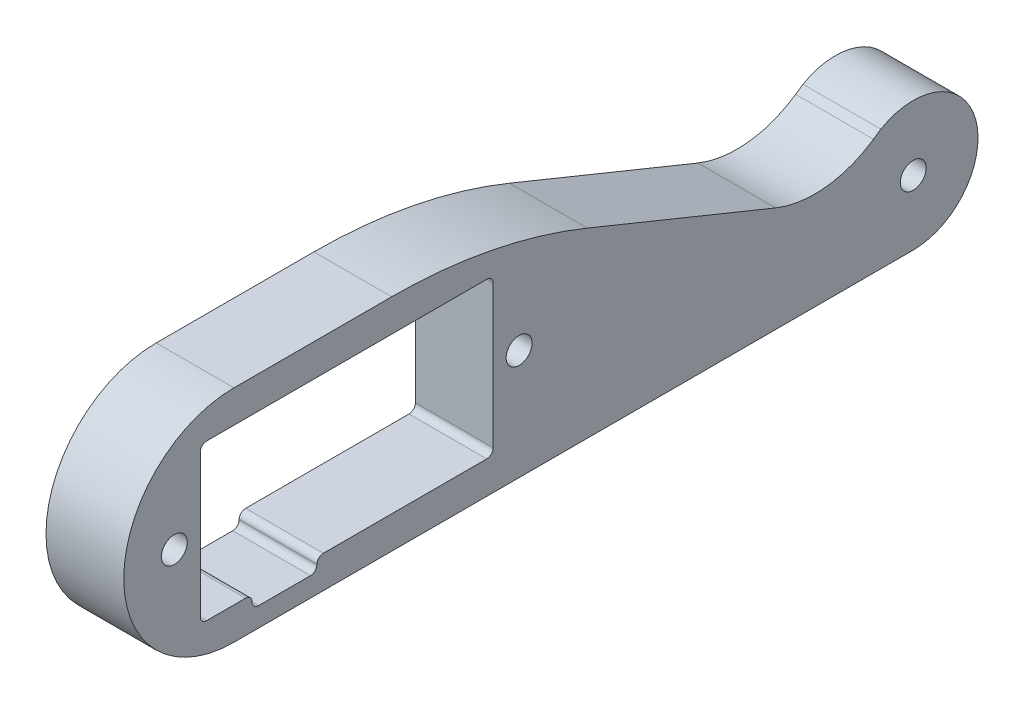
SolidWorks part; units mm, degrees
ref_plane "Piano frontale" through (0, 0, 0) normal (0, 0, 1) x (1, 0, 0)
ref_plane "Piano superiore" through (0, 0, 0) normal (0, 1, 0) x (1, 0, 0)
ref_plane "Piano destro" through (0, 0, 0) normal (1, 0, 0) x (0, 0, -1)
sketch "Schizzo1" plane through (0, 0, 0) normal (1, 0, 0) x (0, 0, -1)
  line L0 (2.6, 14.5) -> (22.6, 14.5)
  line L1 (0, 12) -> (22.6, 12)
  line L2 (0, 12) -> (0, 0)
  line L3 (0, 0) -> (22.6, 0)
  line L4 (22.6, 12) -> (22.6, 0)
  line L5 (22.6, 14.5) -> (48.3781, 4)
  line L6 (48.3781, 4) -> (52.5, 6.8301)
  line L7 (2.6, -2.5) -> (55, -2.5)
  line L9 (4, 0) -> (9, 0)
  line L10 (4, 0) -> (4, -1)
  line L11 (4, -1) -> (9, -1)
  line L12 (9, 0) -> (9, -1)
  circle A0 centre (55, 2.5) radius 5
  arc A2 (2.6, -2.5) -> (2.6, 14.5) centre (2.6, 6) cw
  circle A3 centre (55, 2.5) radius 1
  circle A4 centre (24.6, 6) radius 1
  circle A5 centre (-2, 6) radius 1
  point P23 (0, 6)
  dimension "D3" = 10
  dimension "D7" = 1.5
  dimension "D11" = 8.5
  dimension "D12" = 2
  dimension "D15" = 2
  dimension "D16" = 2
  dimension "D1" = 22.6
  dimension "D2" = 12
  dimension "D4" = 2.5
  dimension "D5" = 2.5
  dimension "D6" = 20
  dimension "D8" = 55
  dimension "D9" = 2.5
  dimension "D10" = 5
  dimension "D13" = 5
  dimension "D14" = 1
  dimension "D17" = 2
  dimension "D18" = 2
  dimension "D19" = 4
extrude "Estrusione-Estrusione1" add sketch "Schizzo1" along normal blind 6 contours A2 L7 A0 L6 L5 L0 A5 A4 L3 L12 L11 L10 L2 L1 L4 | A0 A3 region at (0, 4.4915, -24.522) region at (0, 0.8803, -50.4194)
fillet "Raccordo1" radius 8 1 edges at (3, 4, -48.3781) type face fillet first side face at (3, 5.4151, -50.439) second side face at (3, 9.25, -35.489)
fillet "Raccordo2" radius 40 1 edges at (3, 14.5, -22.6) type face fillet first side face at (3, 14.5, -12.6) second side face at (3, 10.0631, -33.4929)
fillet "Raccordo3" radius 0.5 8 edges at (3, 0, -22.6) (3, 0, 0) (3, 12, 0) (3, 12, -22.6) (3, 0, -4) (3, -1, -4) (3, -1, -9) (3, 0, -9)
